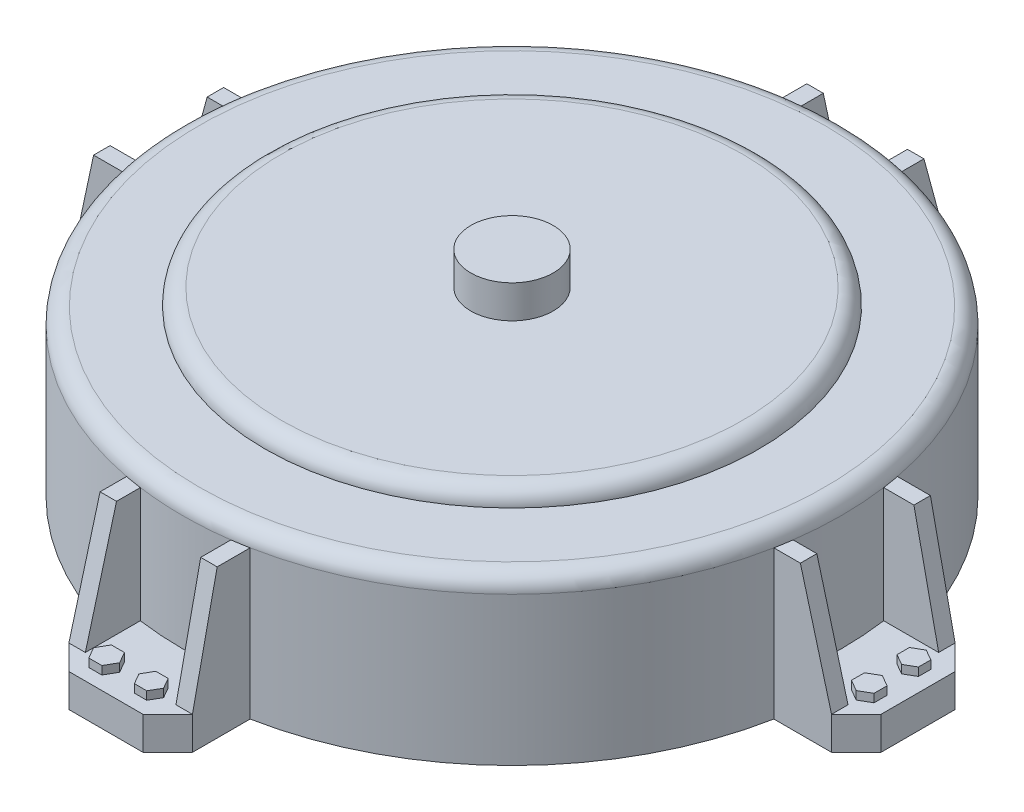
SolidWorks part; units mm, degrees
ref_plane "Front Plane" through (0, 0, 0) normal (0, 0, 1) x (1, 0, 0)
ref_plane "Top Plane" through (0, 0, 0) normal (0, 1, 0) x (1, 0, 0)
ref_plane "Right Plane" through (0, 0, 0) normal (1, 0, 0) x (0, 0, -1)
sketch "Sketch2" plane through (0, 0, 0) normal (0, 1, 0) x (1, 0, 0)
  circle A0 centre (-3.2162, 3.3399) radius 50.8
  dimension "D1" = 101.6
extrude "Boss-Extrude1" add sketch "Sketch2" along normal blind 25.4
fillet "Fillet1" radius 2.54 1 edges at (-3.2162, 25.4, 47.4601)
sketch "Sketch3" plane through (0, 25.4, 0) normal (0, 1, 0) x (1, 0, 0)
  line L0 (-3.2162, 3.3399) -> (-95.0137, 3.3399) construction
  line L1 (-53.1152, 12.8649) -> (-65.8152, 12.8649)
  line L2 (-65.8152, 12.8649) -> (-65.8152, -6.1851)
  line L3 (-65.8152, -6.1851) -> (-53.1152, -6.1851)
  circle A0 centre (-3.2162, 3.3399) radius 50.8 construction
  arc A1 (-53.1152, 12.8649) -> (-53.1152, -6.1851) centre (-3.2162, 3.3399) ccw
  dimension "D1" = 19.05
  dimension "D2" = 12.7
extrude "Boss-Extrude2" add sketch "Sketch3" along normal blind 5.08 from offset 25.4 offset against normal yes
chamfer "Chamfer1" distance 3.81 angle 45 2 edges at (-65.8152, 2.54, -12.8649) (-65.8152, 2.54, 6.1851)
sketch "Sketch4" plane through (0, 0, 6.1851) normal (0, 0, 1) x (1, 0, 0)
  line L0 (-53.1152, 5.08) -> (-53.1152, 22.86)
  line L1 (-54.0162, 22.86) -> (47.5838, 22.86) construction
  line L2 (-53.1152, 22.86) -> (-58.1952, 22.86)
  line L3 (-58.1952, 22.86) -> (-62.0052, 5.08)
  line L4 (-62.0052, 5.08) -> (-53.1152, 5.08)
  dimension "D1" = 3.81
extrude "Boss-Extrude3" add sketch "Sketch4" against normal blind 2.54
sketch "Sketch5" plane through (0, 5.08, 0) normal (0, 1, 0) x (1, 0, 0)
  line L0 (-53.9999, 4.627) -> (-105.0088, 4.627) construction
  line L1 (-62.0052, 12.8649) -> (-62.0052, -6.1851) construction
  line L2 (-58.1952, -6.1851) -> (-62.0052, -6.1851) construction
  line L3 (-65.8152, -2.3751) -> (-62.0052, -6.1851) construction
  line L5 (-63.655, -0.7876) -> (-62.0052, -1.7401)
  line L6 (-62.0052, -1.7401) -> (-60.3554, -0.7876)
  line L7 (-60.3554, -0.7876) -> (-60.3554, 1.1174)
  line L8 (-60.3554, 1.1174) -> (-62.0052, 2.0699)
  line L9 (-62.0052, 2.0699) -> (-63.655, 1.1174)
  line L10 (-63.655, 1.1174) -> (-63.655, -0.7876)
  arc A0 (-53.1152, 12.8649) -> (-53.5337, -3.6451) centre (-3.2162, 3.3399) ccw construction
  circle A1 centre (-62.0052, 0.1649) radius 1.6498 construction
  point P13 (0, 0)
  point P21 (-62.0052, 0.5657)
  point P22 (0, 0)
  dimension "D1" = 1.905
  dimension "D2" = 3.81
extrude "Boss-Extrude4" add sketch "Sketch5" along normal blind 1.27
sketch "Sketch7" plane through (0, 5.08, 0) normal (0, 1, 0) x (1, 0, 0)
  line L0 (-85.8982, 3.3399) -> (0, 3.3399) construction
sketch "Sketch8" plane through (0, 5.08, 0) normal (0, 1, 0) x (1, 0, 0)
  line L0 (-62.0052, 12.8649) -> (-62.0052, -6.1851) construction
sketch "Sketch10" plane through (0, 0, -12.8649) normal (0, 0, -1) x (-1, 0, 0)
  line L0 (53.1152, 5.08) -> (53.1152, 22.86)
  line L1 (54.0162, 22.86) -> (-47.5838, 22.86) construction
  line L2 (53.1152, 22.86) -> (57.1992, 22.86)
  line L3 (53.5337, 22.86) -> (58.1952, 22.86) construction
  line L4 (57.1992, 22.86) -> (62.0052, 5.08)
  line L5 (62.0052, 5.08) -> (53.1152, 5.08)
extrude "Boss-Extrude6" add sketch "Sketch10" against normal blind 2.54
sketch "Sketch11" plane through (0, 5.08, 0) normal (0, 1, 0) x (1, 0, 0)
  line L0 (-62.0052, 12.8649) -> (-62.0052, -6.1851) construction
  line L1 (-63.7457, 6.0462) -> (-62.0052, 5.0413)
  line L2 (-62.0052, 5.0413) -> (-60.2647, 6.0462)
  line L3 (-60.2647, 6.0462) -> (-60.2647, 8.0559)
  line L4 (-60.2647, 8.0559) -> (-62.0052, 9.0608)
  line L5 (-62.0052, 9.0608) -> (-63.7457, 8.0559)
  line L6 (-63.7457, 8.0559) -> (-63.7457, 6.0462)
  circle A0 centre (-62.0052, 7.051) radius 1.7405 construction
  point P1 (0, 0)
  point P11 (0, 0)
  point P12 (0, 0)
  point P13 (0, 0)
extrude "Boss-Extrude7" add sketch "Sketch11" along normal blind 1.27
pattern_circular "CirPattern1" count 4 over 360 about axis through (-3.2162, 25.4, -3.3399) along (0, 1, 0) of "Boss-Extrude6", "Boss-Extrude3", "Boss-Extrude2", "Chamfer1"
pattern_circular "CirPattern2" count 4 over 360 about axis through (-3.2162, 25.4, -3.3399) along (0, 1, 0) of "Boss-Extrude7", "Boss-Extrude4"
sketch "Sketch12" plane through (0, 25.4, 0) normal (0, 1, 0) x (1, 0, 0)
  circle A0 centre (-3.2162, 3.3399) radius 38.1
  circle A2 centre (-3.2162, 3.3399) radius 48.26 construction
  dimension "D1" = 76.2
extrude "Boss-Extrude8" add sketch "Sketch12" along normal blind 2.54
fillet "Fillet2" radius 2.54 1 edges at (-3.2162, 27.94, 34.7601)
sketch "Sketch13" plane through (0, 27.94, 0) normal (0, 1, 0) x (1, 0, 0)
  circle A0 centre (-3.2162, 3.3399) radius 6.35
  circle A2 centre (-3.2162, 3.3399) radius 35.56 construction
  dimension "D1" = 12.7
extrude "Boss-Extrude9" add sketch "Sketch13" along normal blind 5.08
